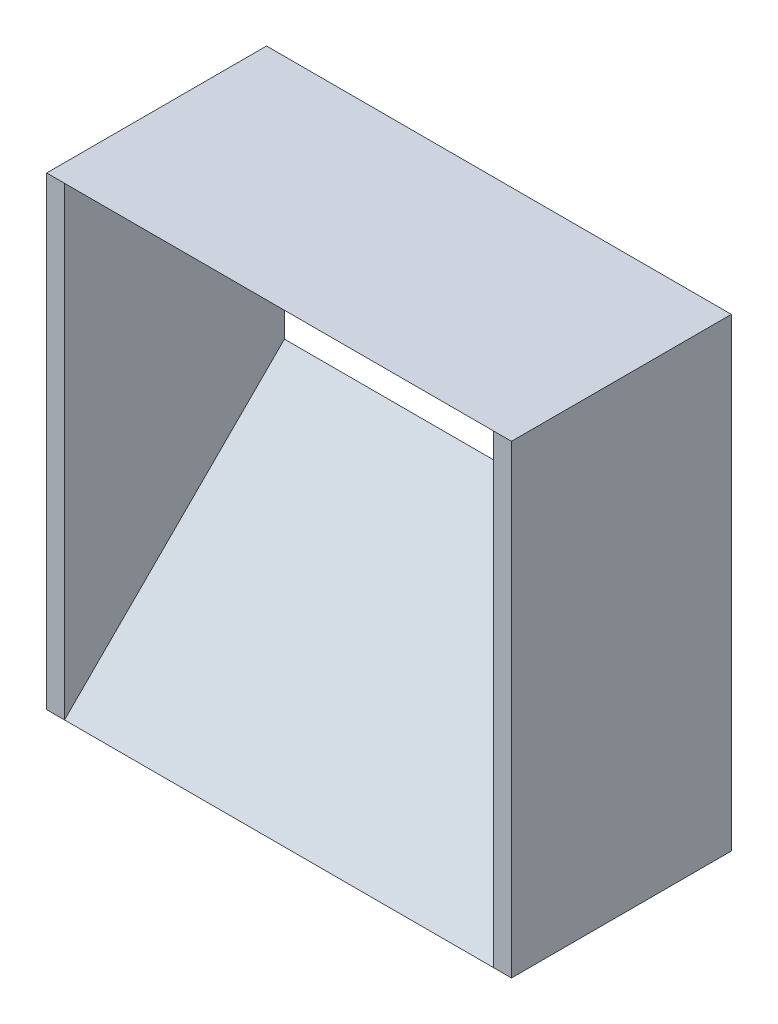
SolidWorks part; units mm, degrees
ref_plane "Front Plane" through (0, 0, 0) normal (1, 0, 0) x (0, 1, 0)
ref_plane "Top Plane" through (0, 0, 0) normal (0, 0, 1) x (0, 1, 0)
ref_plane "Right Plane" through (0, 0, 0) normal (0, 1, 0) x (-1, 0, 0)
sketch "Sketch1" plane through (0, 0, 0) normal (1, 0, 0) x (0, 1, 0)
  line L0 (-3.5, 0) -> (3.5, 0) construction
  line L1 (3.5, 0) -> (65, 61.5)
  line L2 (-65, 61.5) -> (-3.5, 0)
  line L3 (3.5, 0) -> (50003.5, 0) construction
  line L4 (-65, 61.5) -> (65, 61.5) construction
  line L5 (-65, 61.5) -> (-65, 0)
  line L6 (65, 61.5) -> (65, 0)
  line L7 (-65, 0) -> (-59, 0)
  line L8 (-59, 0) -> (-59, 49.5)
  line L9 (-3.5, 0) -> (-9.5, 0)
  line L10 (-59, 49.5) -> (-9.5, 0)
  line L11 (0, 0) -> (0, 70.0357) construction
  line L12 (59, 0) -> (59, 49.5)
  line L13 (65, 0) -> (59, 0)
  line L14 (3.5, 0) -> (9.5, 0)
  line L15 (59, 49.5) -> (9.5, 0)
  point P4 (0, 0)
  dimension "D1" = 7
  dimension "D2" = 130
  dimension "D3" = 45
  dimension "D5" = 6
  dimension "D6" = 6
extrude "Boss-Extrude1" add sketch "Sketch1" along normal blind 60 and the other way blind 60
sketch "Sketch2" plane through (60, 0, 0) normal (1, 0, 0) x (0, 1, 0)
  line L1 (-65, 61.5) -> (65, 61.5)
  line L2 (-65, 61.5) -> (-65, 0)
  line L3 (-65, 0) -> (65, 0)
  line L4 (65, 61.5) -> (65, 0)
extrude "Boss-Extrude2" add sketch "Sketch2" along normal blind 5
mirror "Mirror1" about plane through (0, 0, 0) normal (1, 0, 0) of "Boss-Extrude2"
